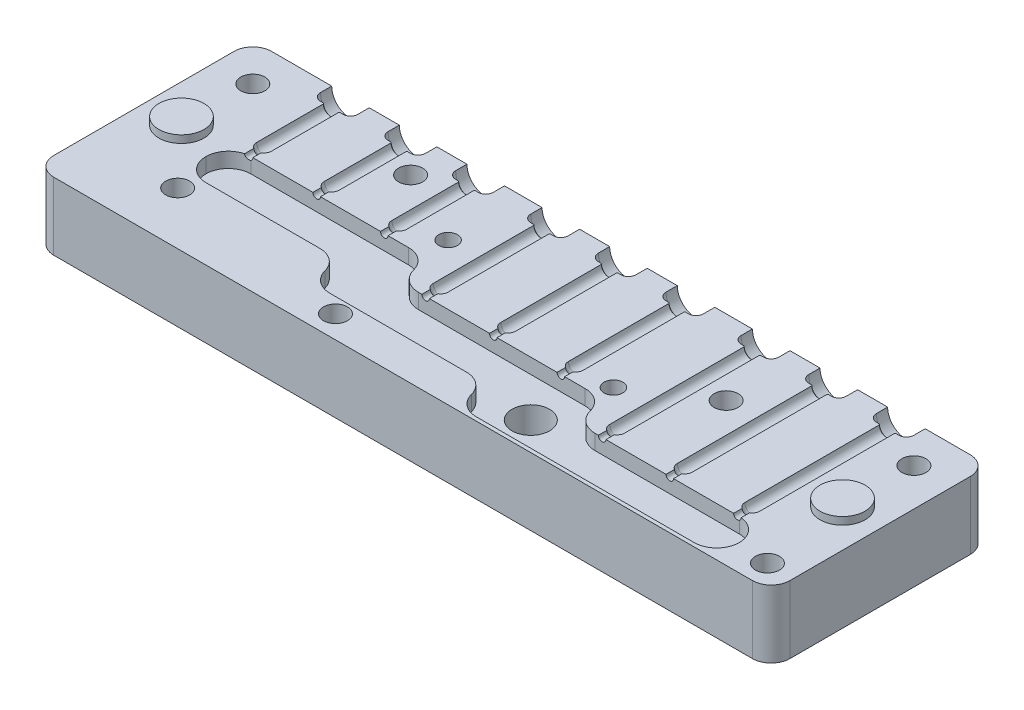
SolidWorks part; units mm, degrees
ref_plane "Ebene vorne" through (0, 0, 0) normal (0, 0, 1) x (1, 0, 0)
ref_plane "Ebene oben" through (0, 0, 0) normal (0, 1, 0) x (1, 0, 0)
ref_plane "Ebene rechts" through (0, 0, 0) normal (1, 0, 0) x (0, 0, -1)
sketch "Skizze1" plane through (0, 0, 0) normal (0, 1, 0) x (1, 0, 0)
  line L1 (0, 0) -> (98, 0)
  line L2 (0, 0) -> (0, 29)
  line L3 (0, 29) -> (98, 29)
  line L4 (98, 0) -> (98, 29)
  dimension "D1" = 98
  dimension "D2" = 29
extrude "Aufsatz-Linear austragen1" add sketch "Skizze1" along normal blind 9
sketch "Skizze2" plane through (0, 0, -29) normal (0, 0, -1) x (-1, 0, 0)
  line L0 (-98, 9) -> (0, 9) construction
  line L1 (-13, 9) -> (-22, 9) construction
  line L2 (-22, 9) -> (-31, 9) construction
  line L3 (-41, 9) -> (-50, 9) construction
  line L4 (-50, 9) -> (-59, 9) construction
  line L5 (-69, 9) -> (-78, 9) construction
  line L6 (-78, 9) -> (-87, 9) construction
  circle A0 centre (-13, 9) radius 1
  circle A1 centre (-22, 9) radius 1
  circle A2 centre (-31, 9) radius 1
  circle A3 centre (-41, 9) radius 1
  circle A4 centre (-50, 9) radius 1
  circle A5 centre (-59, 9) radius 1
  circle A6 centre (-69, 9) radius 1
  circle A7 centre (-78, 9) radius 1
  circle A8 centre (-87, 9) radius 1
  dimension "D1" = 2
  dimension "D2" = 9
  dimension "D3" = 13
  dimension "D5" = 10
  dimension "D4" = 3
extrude "Schnitt-Linear austragen1" cut sketch "Skizze2" against normal blind 12.5 contours A0 | A1 | A2
fillet "Verrundung5" radius 2.5 4 edges at (98, 4.5, 0) (98, 4.5, -29) (0, 4.5, -29) (0, 4.5, 0)
extrude "Schnitt-Linear austragen2" cut sketch "Skizze2<4>" against normal blind 17 contours A3 | A4 | A5
sketch "Skizze2<4>" plane through (0, 0, -29) normal (0, 0, -1) x (-1, 0, 0) same geometry as "Skizze2"
extrude "Schnitt-Linear austragen3" cut sketch "Skizze2<5>" against normal blind 21.5 contours A6 | A7 | A8
sketch "Skizze2<5>" plane through (0, 0, -29) normal (0, 0, -1) x (-1, 0, 0) same geometry as "Skizze2"
sketch "Skizze4" plane through (0, 0, -29) normal (0, 0, -1) x (-1, 0, 0)
  circle A0 centre (-13, 9) radius 2.5
  circle A1 centre (-22, 9) radius 2.5
  circle A2 centre (-31, 9) radius 2.5
  arc A3 (-14, 9) -> (-12, 9) centre (-13, 9) ccw construction
  arc A4 (-23, 9) -> (-21, 9) centre (-22, 9) ccw construction
  arc A5 (-32, 9) -> (-30, 9) centre (-31, 9) ccw construction
  circle A6 centre (-41, 9) radius 2.5
  circle A7 centre (-50, 9) radius 2.5
  circle A8 centre (-59, 9) radius 2.5
  circle A9 centre (-69, 9) radius 2.5
  circle A10 centre (-78, 9) radius 2.5
  circle A11 centre (-87, 9) radius 2.5
  dimension "D1" = 5
  dimension "D2" = 3
extrude "Schnitt-Linear austragen4" cut sketch "Skizze4" against normal blind 2.5
fillet "Verrundung1" radius 1 18 edges at (87, 6.5, -26.5) (78, 6.5, -26.5) (69, 6.5, -26.5) (59, 6.5, -26.5) (50, 6.5, -26.5) (41, 6.5, -26.5) (31, 6.5, -26.5) (22, 6.5, -26.5) (13, 6.5, -26.5) (13, 8, -16.5) (22, 8, -16.5) (31, 8, -16.5) (41, 8, -12) (50, 8, -12) (59, 8, -12) (69, 8, -7.5) (78, 8, -7.5) (87, 8, -7.5)
chamfer "Fase1" distance 0.1 angle 45 9 edges at (22, 8, -26.5) (13, 8, -26.5) (31, 8, -26.5) (59, 8, -26.5) (50, 8, -26.5) (41, 8, -26.5) (69, 8, -26.5) (78, 8, -26.5) (87, 8, -26.5)
sketch "Skizze5" plane through (0, 9, 0) normal (0, 1, 0) x (1, 0, 0)
  line L0 (13, 16.5) -> (13, 15.5) construction
  line L1 (41, 12) -> (41, 11) construction
  line L2 (12.75, 15.5) -> (13, 15.5)
  line L3 (12.75, 17.5) -> (12.75, 15.5)
  line L4 (13.25, 15.5) -> (13, 15.5)
  line L5 (40.75, 11) -> (41, 11)
  line L6 (40.75, 13) -> (40.75, 11)
  line L7 (41, 11) -> (41.25, 11)
  line L8 (12.75, 17.5) -> (13.25, 17.5)
  line L9 (69, 7.5) -> (69, 6.5) construction
  line L10 (21.75, 15.5) -> (22, 15.5)
  line L11 (41.25, 12) -> (41.25, 11) construction
  line L12 (40.75, 12) -> (40.75, 11) construction
  line L13 (40.75, 13) -> (41.25, 13)
  line L14 (68.75, 6.5) -> (69, 6.5)
  line L15 (68.75, 8.5) -> (68.75, 6.5)
  line L16 (69, 6.5) -> (69.25, 6.5)
  line L17 (68.75, 7.5) -> (68.75, 6.5) construction
  line L18 (13.25, 17.5) -> (13.25, 15.5)
  line L19 (41.25, 13) -> (41.25, 11)
  line L20 (21.75, 17.5) -> (21.75, 15.5)
  line L21 (22.25, 15.5) -> (22, 15.5)
  line L22 (69.25, 7.5) -> (69.25, 6.5) construction
  line L23 (68.75, 8.5) -> (69.25, 8.5)
  line L24 (69.25, 8.5) -> (69.25, 6.5)
  line L25 (49.75, 11) -> (50, 11)
  line L26 (49.75, 13) -> (49.75, 11)
  line L27 (13.25, 16.5) -> (13.25, 15.5) construction
  line L28 (12.75, 16.5) -> (12.75, 15.5) construction
  line L29 (21.75, 17.5) -> (22.25, 17.5)
  line L30 (22.25, 17.5) -> (22.25, 15.5)
  line L31 (22, 16.5) -> (22, 15.5) construction
  line L32 (30.75, 15.5) -> (31, 15.5)
  line L33 (30.75, 17.5) -> (30.75, 15.5)
  line L34 (31.25, 15.5) -> (31, 15.5)
  line L35 (30.75, 17.5) -> (31.25, 17.5)
  line L36 (31.25, 17.5) -> (31.25, 15.5)
  line L37 (31, 16.5) -> (31, 15.5) construction
  line L38 (50, 11) -> (50.25, 11)
  line L39 (49.75, 13) -> (50.25, 13)
  line L40 (50.25, 13) -> (50.25, 11)
  line L41 (50, 12) -> (50, 11) construction
  line L42 (58.75, 11) -> (59, 11)
  line L43 (58.75, 13) -> (58.75, 11)
  line L44 (59, 11) -> (59.25, 11)
  line L45 (58.75, 13) -> (59.25, 13)
  line L46 (59.25, 13) -> (59.25, 11)
  line L47 (59, 12) -> (59, 11) construction
  line L48 (77.75, 6.5) -> (78, 6.5)
  line L49 (77.75, 8.5) -> (77.75, 6.5)
  line L50 (78, 6.5) -> (78.25, 6.5)
  line L51 (77.75, 8.5) -> (78.25, 8.5)
  line L52 (78.25, 8.5) -> (78.25, 6.5)
  line L53 (78, 7.5) -> (78, 6.5) construction
  line L54 (86.75, 6.5) -> (87, 6.5)
  line L55 (86.75, 8.5) -> (86.75, 6.5)
  line L56 (87, 6.5) -> (87.25, 6.5)
  line L57 (86.75, 8.5) -> (87.25, 8.5)
  line L58 (87.25, 8.5) -> (87.25, 6.5)
  line L59 (87, 7.5) -> (87, 6.5) construction
  dimension "D1" = 1
  dimension "D2" = 0.5
  dimension "D4" = 9
  dimension "D5" = 3
  dimension "D6" = 9
  dimension "D8" = 9
  dimension "D3" = 3
  dimension "D7" = 3
extrude "Schnitt-Linear austragen5" cut sketch "Skizze5" against normal blind 0.25
sketch "Skizze6" plane through (0, 9, 0) normal (0, 1, 0) x (1, 0, 0)
  line L0 (37.25, 15.5) -> (10.25, 15.5)
  line L1 (37.25, 11) -> (65.25, 11)
  line L2 (37.25, 15.5) -> (37.25, 11)
  line L3 (31.25, 15.5) -> (31.25, 16.5318) construction
  line L4 (49.75, 11) -> (50.25, 11) construction
  line L5 (65.25, 11) -> (65.25, 6.5)
  line L6 (65.25, 6.5) -> (90.25, 6.5)
  line L7 (10.25, 15.5) -> (10.25, 9.5)
  line L8 (10.25, 9.5) -> (31.25, 9.5)
  line L9 (31.25, 9.5) -> (31.25, 5)
  line L10 (31.25, 5) -> (55.25, 5)
  line L11 (55.25, 5) -> (55.25, 0.5)
  line L12 (55.25, 0.5) -> (90.25, 0.5)
  line L13 (90.25, 0.5) -> (90.25, 6.5)
  line L14 (65.25, 6.5) -> (55.25, 6.5) construction
  line L15 (37.25, 11) -> (37.25, 5) construction
  line L16 (31.25, 9.5) -> (37.25, 9.5) construction
  line L17 (59.25, 11) -> (59.25, 12.0318) construction
  line L18 (86.75, 6.5) -> (87.25, 6.5) construction
  line L19 (12.75, 15.5) -> (13.25, 15.5) construction
  dimension "D1" = 6
  dimension "D2" = 6
  dimension "D3" = 6
  dimension "D4" = 10
  dimension "D5" = 2.5
  dimension "D6" = 3
extrude "Schnitt-Linear austragen6" cut sketch "Skizze6" against normal blind 2
sketch "Skizze7" plane through (0, 7, 0) normal (0, 1, 0) x (1, 0, 0)
  line L0 (55.25, 5) -> (65.25, 6.5) construction
  circle A0 centre (60.25, 5.75) radius 2.5
  dimension "D1" = 5
extrude "Schnitt-Linear austragen7" cut sketch "Skizze7" against normal up to next
fillet "Verrundung2" radius 3 8 edges at (90.25, 8, -0.5) (90.25, 8, -6.5) (65.25, 8, -11) (55.25, 8, -0.5) (37.25, 8, -15.5) (31.25, 8, -5) (10.25, 8, -9.5) (10.25, 8, -15.5)
fillet "Verrundung6" radius 3 4 edges at (65.25, 8, -6.5) (55.25, 8, -5) (31.25, 8, -9.5) (37.25, 8, -11)
sketch "Skizze15" plane through (0, 0, -29) normal (0, 0, -1) x (-1, 0, 0)
  line L0 (-87.5, 9) -> (-86.5, 9)
  line L1 (-78.5, 9) -> (-77.5, 9)
  line L2 (-69.5, 9) -> (-68.5, 9)
  line L3 (-59.5, 9) -> (-58.5, 9)
  line L4 (-50.5, 9) -> (-49.5, 9)
  line L5 (-41.5, 9) -> (-40.5, 9)
  line L6 (-31.5, 9) -> (-30.5, 9)
  line L7 (-22.5, 9) -> (-21.5, 9)
  line L8 (-13.5, 9) -> (-12.5, 9)
  arc A0 (-87.5, 9) -> (-86.5, 9) centre (-87, 9) ccw
  arc A1 (-89.5, 9) -> (-84.5, 9) centre (-87, 9) ccw construction
  arc A2 (-78.5, 9) -> (-77.5, 9) centre (-78, 9) ccw
  arc A3 (-69.5, 9) -> (-68.5, 9) centre (-69, 9) ccw
  arc A4 (-80.5, 9) -> (-75.5, 9) centre (-78, 9) ccw construction
  arc A5 (-59.5, 9) -> (-58.5, 9) centre (-59, 9) ccw
  arc A6 (-50.5, 9) -> (-49.5, 9) centre (-50, 9) ccw
  arc A7 (-41.5, 9) -> (-40.5, 9) centre (-41, 9) ccw
  arc A8 (-31.5, 9) -> (-30.5, 9) centre (-31, 9) ccw
  arc A9 (-22.5, 9) -> (-21.5, 9) centre (-22, 9) ccw
  arc A10 (-13.5, 9) -> (-12.5, 9) centre (-13, 9) ccw
  arc A11 (-61.5, 9) -> (-56.5, 9) centre (-59, 9) ccw construction
  dimension "D1" = 1
  dimension "D2" = 3
  dimension "D3" = 3
extrude "Schnitt-Linear austragen8" cut sketch "Skizze15" against normal up to next
hole_wizard "Durchgangsloch für M31" positions "Skizze9" profile "Skizze8" hole size "M3" standard "DIN" end condition through all
sketch "Skizze9" plane through (0, 9, 0) normal (0, 1, 0) x (1, 0, 0)
  line L0 (0, 26.5) -> (0, 2.5) construction
  line L1 (10.5, 29) -> (2.5, 29) construction
  line L2 (5, 24) -> (26, 24)
  line L5 (26, 24) -> (93, 24)
  line L7 (98, 2.5) -> (98, 26.5) construction
  line L8 (94.5, 3) -> (37, 3)
  line L9 (37, 3) -> (12, 3)
  line L10 (12, 3) -> (12, 7)
  line L12 (2.5, 0) -> (95.5, 0) construction
  point P0 (26, 24)
  point P2 (73, 19)
  point P4 (93, 24)
  point P6 (94.5, 3)
  point P8 (12, 7)
  point P10 (5, 24)
  point P34 (37, 3)
  dimension "D1" = 5
  dimension "D2" = 5
  dimension "D3" = 26
  dimension "D4" = 5
  dimension "D5" = 25
  dimension "D6" = 5
  dimension "D7" = 12
  dimension "D8" = 3.5
  dimension "D9" = 3
  dimension "D10" = 4
  dimension "D11" = 25
sketch "Skizze8" plane through (26, 9, -24) normal (1, 0, 0) x (0, 0, 1)
  line L0 (0, 0) -> (0, 9)
  line L1 (0, 9) -> (1.6, 9)
  line L2 (1.6, 9) -> (1.6, 0)
  line L5 (1.6, 0) -> (0, 0)
  line L11 (0, -6.35) -> (0, 107.95) construction
  dimension "Bohrerdurchmesser" = 3.2
  dimension "Bohrungstiefe" = 9
hole_wizard "M3 Gewindebohrung1" positions "Skizze14" profile "Skizze13" tap size "M3" standard "DIN" end condition through all
sketch "Skizze14" plane through (0, 9, 0) normal (0, 1, 0) x (1, 0, 0)
  line L0 (36, 29) -> (36, 0)
  line L1 (38.5, 29) -> (33.5, 29) construction
  line L2 (2.5, 0) -> (95.5, 0) construction
  line L4 (66.5, 29) -> (61.5, 29) construction
  line L5 (64, 29) -> (64, 0)
  point P0 (36, 19)
  point P2 (64, 13)
  dimension "D1" = 10
  dimension "D2" = 16
sketch "Skizze13" plane through (36, 9, -19) normal (1, 0, 0) x (0, 0, 1)
  line L0 (0, 0) -> (0, 9)
  line L1 (0, 9) -> (1.25, 9)
  line L2 (1.25, 9) -> (1.25, 0)
  line L5 (1.25, 0) -> (0, 0)
  line L11 (0, -6.35) -> (0, 107.95) construction
  dimension "Bohrerdurchmesser" = 2.5
  dimension "Bohrungstiefe" = 9
cosmetic thread "Bohrungsgewinde1" parameters "D2"=3
cosmetic thread "Bohrungsgewinde2" parameters "D2"=3
sketch "Skizze10" plane through (0, 9, 0) normal (0, 1, 0) x (1, 0, 0)
  line L0 (0, 14.5) -> (5, 14.5) construction
  line L1 (0, 26.5) -> (0, 2.5) construction
  line L2 (5, 14.5) -> (93, 14.5) construction
  line L3 (93, 14.5) -> (98, 14.5) construction
  line L4 (98, 2.5) -> (98, 26.5) construction
  circle A0 centre (5, 14.5) radius 3
  circle A1 centre (93, 14.5) radius 3
  dimension "D1" = 6
  dimension "D2" = 5
extrude "Aufsatz-Linear austragen2" add sketch "Skizze10" along normal blind 1 contours A1 | A0 region at (5, 9, -14.5) region at (93, 9, -14.5)
sketch "Skizze17" plane through (0, 9, 0) normal (0, 1, 0) x (1, 0, 0)
  line L0 (13, 17.384) -> (13, 14.75)
  line L1 (22, 17.384) -> (22, 14.75)
  line L2 (31, 17.384) -> (31, 14.75)
  line L3 (13, 14.75) -> (22, 14.75)
  line L4 (22, 14.75) -> (31, 14.75)
  line L5 (41, 12.884) -> (41, 10.25)
  line L6 (50, 12.884) -> (50, 10.25)
  line L7 (59, 12.884) -> (59, 10.25)
  line L8 (59, 10.25) -> (50, 10.25)
  line L9 (50, 10.25) -> (41, 10.25)
  line L10 (87, 8.384) -> (87, 5.75)
  line L11 (78, 8.384) -> (78, 5.75)
  line L12 (69, 8.384) -> (69, 5.75)
  line L13 (69, 5.75) -> (78, 5.75)
  line L14 (87, 5.75) -> (78, 5.75)
  line L15 (77.5, 6.5) -> (69.5, 6.5) construction
  line L16 (58.5, 11) -> (50.5, 11) construction
  line L17 (21.5, 15.5) -> (13.5, 15.5) construction
  line L18 (13.5, 16.634) -> (12.5, 16.634) construction
  dimension "D1" = 0.75
  dimension "D2" = 0.75
  dimension "D3" = 0.75
  dimension "D4" = 0.75
sketch "Skizze18" plane through (0, 9, 0) normal (0, 1, 0) x (1, 0, 0)
  line L0 (87, 30) -> (87, 8.5)
  line L2 (86, 8.5) -> (88, 8.5) construction
  line L3 (95.5, 29) -> (89.5, 29) construction
  line L4 (59, 13) -> (59, 30)
  line L5 (66.5, 29) -> (61.5, 29) construction
  line L6 (58, 13) -> (60, 13) construction
  line L7 (31, 17.5) -> (31, 30)
  line L8 (38.5, 29) -> (33.5, 29) construction
  line L9 (30, 17.5) -> (32, 17.5) construction
  line L10 (78, 30) -> (78, 8.5)
  line L11 (50, 13) -> (50, 30)
  line L12 (22, 17.5) -> (22, 30)
  line L13 (69, 30) -> (69, 8.5)
  line L14 (41, 13) -> (41, 30)
  line L15 (13, 17.5) -> (13, 30)
  line L16 (77, 8.5) -> (79, 8.5) construction
  dimension "D1" = 1
  dimension "D2" = 1
  dimension "D3" = 1
  dimension "D4" = 3
sketch "Skizze12" plane through (0, 0, -29) normal (0, 0, -1) x (-1, 0, 0)
  line L0 (-95.5, 0) -> (-2.5, 0) construction
  line L1 (-88.5, 5.5) -> (-85.5, 5.5)
  line L2 (-88.5, 5.5) -> (-88.5, 0)
  line L3 (-88.5, 0) -> (-85.5, 0)
  line L4 (-85.5, 5.5) -> (-85.5, 0)
  line L5 (-69, 5.5) -> (-69, 6.5) construction
  line L6 (-79.5, 5.5) -> (-76.5, 5.5)
  line L7 (-79.5, 5.5) -> (-79.5, 0)
  line L8 (-79.5, 0) -> (-76.5, 0)
  line L9 (-76.5, 5.5) -> (-76.5, 0)
  line L10 (-70.5, 5.5) -> (-67.5, 5.5)
  line L11 (-70.5, 5.5) -> (-70.5, 0)
  line L12 (-70.5, 0) -> (-67.5, 0)
  line L13 (-67.5, 5.5) -> (-67.5, 0)
  line L14 (-60.5, 5.5) -> (-57.5, 5.5)
  line L15 (-78, 6.5) -> (-78, 5.5) construction
  line L16 (-60.5, 5.5) -> (-60.5, 0)
  line L17 (-87, 6.5) -> (-87, 5.5) construction
  line L18 (-60.5, 0) -> (-57.5, 0)
  line L19 (-57.5, 5.5) -> (-57.5, 0)
  line L20 (-51.5, 5.5) -> (-48.5, 5.5)
  line L21 (-51.5, 5.5) -> (-51.5, 0)
  line L22 (-51.5, 0) -> (-48.5, 0)
  line L23 (-48.5, 5.5) -> (-48.5, 0)
  line L24 (-42.5, 5.5) -> (-39.5, 5.5)
  line L25 (-42.5, 5.5) -> (-42.5, 0)
  line L26 (-42.5, 0) -> (-39.5, 0)
  line L27 (-39.5, 5.5) -> (-39.5, 0)
  line L28 (-41, 5.5) -> (-41, 6.5) construction
  line L29 (-50, 6.5) -> (-50, 5.5) construction
  line L30 (-59, 6.5) -> (-59, 5.5) construction
  line L31 (-32.5, 5.5) -> (-29.5, 5.5)
  line L32 (-32.5, 5.5) -> (-32.5, 0)
  line L33 (-32.5, 0) -> (-29.5, 0)
  line L34 (-29.5, 5.5) -> (-29.5, 0)
  line L35 (-23.5, 5.5) -> (-20.5, 5.5)
  line L36 (-23.5, 5.5) -> (-23.5, 0)
  line L37 (-23.5, 0) -> (-20.5, 0)
  line L38 (-20.5, 5.5) -> (-20.5, 0)
  line L39 (-14.5, 5.5) -> (-11.5, 5.5)
  line L40 (-14.5, 5.5) -> (-14.5, 0)
  line L41 (-14.5, 0) -> (-11.5, 0)
  line L42 (-11.5, 5.5) -> (-11.5, 0)
  line L43 (-13, 5.5) -> (-13, 6.5) construction
  line L44 (-22, 6.5) -> (-22, 5.5) construction
  line L45 (-31, 6.5) -> (-31, 5.5) construction
  arc A0 (-71.5, 9) -> (-66.5, 9) centre (-69, 9) ccw construction
  arc A1 (-80.5, 9) -> (-75.5, 9) centre (-78, 9) ccw construction
  arc A2 (-89.5, 9) -> (-84.5, 9) centre (-87, 9) ccw construction
  arc A3 (-61.5, 9) -> (-56.5, 9) centre (-59, 9) ccw construction
  point P14 (-87, 5.5)
  point P15 (-78, 5.5)
  point P16 (-69, 5.5)
  point P46 (-59, 5.5)
  point P47 (-50, 5.5)
  point P48 (-41, 5.5)
  point P67 (-31, 5.5)
  point P68 (-22, 5.5)
  point P69 (-13, 5.5)
  dimension "D1" = 1
  dimension "D2" = 6
  dimension "D3" = 3
extrude "Aufsatz-Linear austragen3" [suppressed] add sketch "Skizze12" along normal blind 8
fillet "Verrundung3" [suppressed] radius 3
fillet "Verrundung4" [suppressed] radius 1
